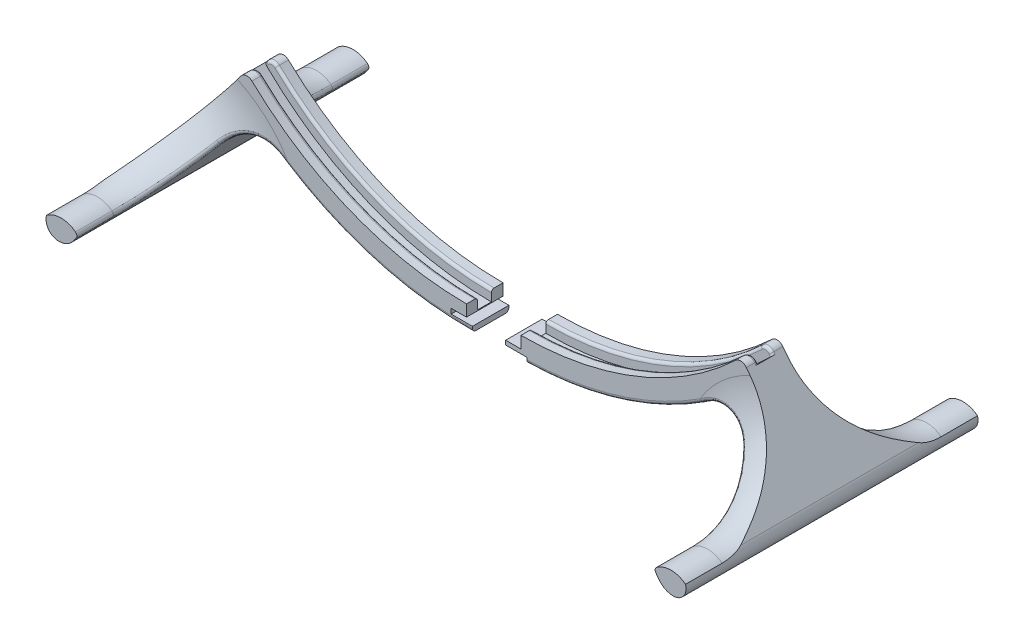
SolidWorks part; units mm, degrees
ref_plane "Top" through (0, 0, 0) normal (0, 0, 1) x (1, 0, 0)
ref_plane "Front" through (0, 0, 0) normal (0, 1, 0) x (1, 0, 0)
ref_plane "Right" through (0, 0, 0) normal (1, 0, 0) x (0, 0, -1)
sketch "Sketch1" plane through (0, 0, 0) normal (0, 0, 1) x (1, 0, 0)
  line L0 (0, 0) -> (0, -105.0764) construction
  line L5 (0, -87.5) -> (-65.4908, -87.5) construction
  line L6 (0, -87.5) -> (71.9118, -87.5) construction
  line L7 (0, 0) -> (-105.0764, -105.0764) construction
  line L9 (0, -91.5) -> (-127.2816, -91.5) construction
  line L10 (0, -91.5) -> (71.9118, -91.5) construction
  line L11 (-60.4576, -60.4576) -> (-81.4636, -88.3948)
  line L12 (-58.4672, -70.3835) -> (-72.7034, -89.3171)
  line L13 (58.4672, -70.3835) -> (72.7034, -89.3171)
  line L14 (60.4576, -60.4576) -> (81.4636, -88.3948)
  circle A0 centre (0, 0) radius 87.5 construction
  circle A1 centre (0, 0) radius 85.5 construction
  circle A2 centre (0, 0) radius 91.5 construction
  arc A3 (-60.4576, -60.4576) -> (60.4576, -60.4576) centre (0, 0) ccw
  arc A5 (-81.4636, -88.3948) -> (-72.7034, -89.3171) centre (-76.8357, -86.5021) ccw
  arc A6 (81.4636, -88.3948) -> (72.7034, -89.3171) centre (76.8357, -86.5021) cw
  arc A7 (-58.4672, -70.3835) -> (0, -91.5) centre (0, 0) ccw
  arc A8 (58.4672, -70.3835) -> (0, -91.5) centre (0, 0) cw
  point P3 (0, -65.9032)
  dimension "D1" = 175
  dimension "D4" = 2
  dimension "D5" = 4
  dimension "D3" = 5
  dimension "D2" = 45
extrude "Boss-Extrude1" add sketch "Sketch1" along normal blind 80 contours A8 L13 A6 L14 A3 L11 A5 L12 A7
sketch "Sketch2" plane through (0, 0, 0) normal (0, 1, 0) x (1, 0, 0)
  line L0 (71.4636, -80) -> (71.4636, -45)
  line L1 (71.4636, -45) -> (-71.4636, -45)
  line L2 (71.4636, 0) -> (71.4636, -35)
  line L3 (71.4636, -35) -> (-71.4636, -35)
  line L4 (-60.4576, -80) -> (60.4576, -80) construction
  line L5 (60.4576, 0) -> (-60.4576, 0) construction
  line L6 (0, -80) -> (0, 0) construction
  line L7 (81.4636, -80) -> (81.4636, 0) construction
  line L8 (71.4636, -80) -> (0, -99.5975)
  line L9 (71.4636, 0) -> (0, 25.5853)
  line L10 (-71.4636, 0) -> (0, 25.5853)
  line L11 (-71.4636, -80) -> (0, -99.5975)
  line L12 (-71.4636, 0) -> (-71.4636, -35)
  line L13 (-71.4636, -80) -> (-71.4636, -45)
  point P20 (0, -35)
  point P21 (0, -45)
  dimension "D1" = 35
  dimension "D2" = 35
  dimension "D3" = 10
extrude "Cut-Extrude1" cut sketch "Sketch2" against normal through all both and the other way through all
fillet "Fillet1" radius 6.5 4 edges at (-71.4636, -75.0952, 17.5) (-71.4636, -75.0952, 62.5) (71.4636, -75.0952, 62.5) (71.4636, -75.0952, 17.5)
fillet "Fillet2" radius 25 4 edges at (76.5459, -85.6711, 45) (76.5459, -85.6711, 35) (-76.5459, -85.6711, 35) (-76.5459, -85.6711, 45)
fillet "Fillet3" radius 10 2 edges at (-58.4672, -70.3835, 40) (58.4672, -70.3835, 40)
fillet "Fillet4" radius 2 2 edges at (60.4576, -60.4576, 40) (-60.4576, -60.4576, 40)
fillet "Fillet5" radius 1 9 edges at (0, -91.5, 35) (71.4636, -87.6682, 5) (69.8099, -85.4688, 21.3523) (58.9029, -74.6534, 34.0242) (-71.4636, -87.6682, 5) (-70.6242, -86.5519, 18.1953) (-57.1856, -74.3762, 34.3891)
fillet "Fillet6" radius 1 9 edges at (0, -91.5, 45) (-71.4636, -87.6682, 75) (-69.8099, -85.4688, 58.6477) (-58.9029, -74.6534, 45.9758) (71.4636, -87.6682, 75) (70.6242, -86.5519, 61.8047) (57.1856, -74.3762, 45.6109)
sketch "Sketch3" plane through (0, 0, 45) normal (0, 0, 1) x (1, 0, 0)
  line L0 (63.7584, -61.1015) -> (-3.5778, -30.4145)
  line L1 (-3.5778, -30.4145) -> (-63.7115, -61.1015)
  arc A0 (63.7584, -61.1015) -> (-63.7115, -61.1015) centre (0.0235, -0.4232) cw
  dimension "D1" = 88
extrude "Cut-Extrude2" cut sketch "Sketch3" against normal blind 3.8 from offset 3 offset against normal yes
fillet "Fillet7" radius 0.75 10 edges at (61.9951, -62.5024, 42) (60.3917, -61.483, 42) (-61.985, -62.489, 42) (-60.3917, -61.483, 42) (61.9951, -62.5024, 38.2) (60.3917, -61.483, 38.2) (-61.985, -62.489, 38.2) (-60.3917, -61.483, 38.2) (0, -85.5, 42) (0, -85.5, 38.2)
fillet "Fillet8" radius 3.5 1 edges at (81.4636, -88.3948, 40)
fillet "Fillet9" radius 3.5 1 edges at (-81.4636, -88.3948, 40)
sketch "Sketch4" plane through (0, 0, 0) normal (0, 0, 1) x (1, 0, 0)
  line L0 (80.2888, -88.0014) -> (-80.2888, -88.0014) construction
  line L1 (0, -88.0014) -> (0, -36.8416) construction
  line L2 (0, -84.6935) -> (0, -88.7011)
  line L3 (0, -88.7011) -> (-4.2046, -88.7011)
  line L4 (-4.2046, -88.7011) -> (-4.2046, -89.9606)
  line L5 (-4.2046, -89.9606) -> (1.6208, -89.9606)
  line L6 (1.6208, -89.9606) -> (1.6208, -91.9501)
  arc A0 (76.6794, -91.4996) -> (80.1505, -87.0273) centre (76.7888, -88.0014) ccw construction
  arc A1 (-80.1505, -87.0273) -> (-76.6794, -91.4996) centre (-76.7888, -88.0014) ccw construction
extrude "Cut-Extrude-Thin1" cut sketch "Sketch4" against normal blind 10 and the other way through all thin thin type mid plane wall 0.1
move or copy body "Body-Move/Copy1" bodies to move or copy 104 copy no translate (14.8233, 0, 0)
other "Save Bodies1"
